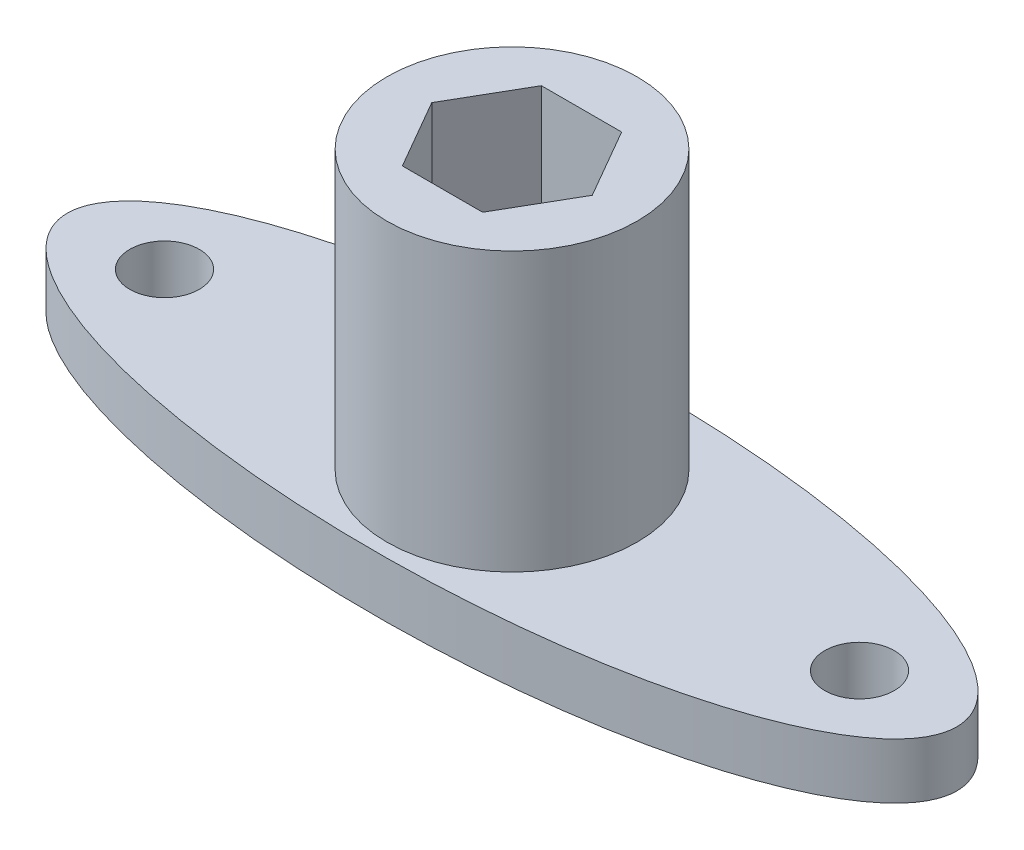
SolidWorks part; units mm, degrees
ref_plane "Front Plane" through (0, 0, 0) normal (0, 0, 1) x (1, 0, 0)
ref_plane "Top Plane" through (0, 0, 0) normal (0, 1, 0) x (1, 0, 0)
ref_plane "Right Plane" through (0, 0, 0) normal (1, 0, 0) x (0, 0, -1)
sketch "Sketch1" plane through (0, 0, 0) normal (0, 1, 0) x (1, 0, 0)
  line L0 (0, 0) -> (0, 8.2104) construction
  line L2 (3.6662, 0) -> (1.8331, 3.175)
  line L3 (1.8331, 3.175) -> (-1.8331, 3.175)
  line L4 (-1.8331, 3.175) -> (-3.6662, 0)
  line L5 (-3.6662, 0) -> (-1.8331, -3.175)
  line L6 (-1.8331, -3.175) -> (1.8331, -3.175)
  line L7 (1.8331, -3.175) -> (3.6662, 0)
  circle A0 centre (-15.875, 0) radius 1.5875
  circle A1 centre (15.875, 0) radius 1.5875
  circle A2 centre (0, 0) radius 5.715
  circle A3 centre (0, 0) radius 3.175 construction
  ellipse E0 centre (0, 0) end of major axis (20.32, 0) minor radius 6.35
  point P14 (0, 0)
  dimension "D3" = 4.445
  dimension "D4" = 3.175
  dimension "D5" = 11.43
  dimension "D1" = 12.7
  dimension "D2" = 40.64
  dimension "D6" = 6.35
extrude "Boss-Extrude1" add sketch "Sketch1" along normal blind 2.54 contours E0 A1 A0 A2 | A2 L7 L6 L5 L4 L3 L2 | L2 L3 L4 L5 L6 L7 region at (-5.5534, 0, 0) region at (-19.8839, 0, 0.179)
extrude "Boss-Extrude3" add sketch "Sketch1<4>" along normal blind 15.24 contours A2 L7 L6 L5 L4 L3 L2 region at (-5.5534, 0, 0)
sketch "Sketch1<4>" plane through (0, 0, 0) normal (0, 1, 0) x (1, 0, 0) same geometry as "Sketch1"
extrude "Boss-Extrude4" add sketch "Sketch1<5>" along normal blind 7.62 contours L6 L7 L2 L3 L4 L5 region at (0, 0, 0)
sketch "Sketch1<5>" plane through (0, 0, 0) normal (0, 1, 0) x (1, 0, 0) same geometry as "Sketch1"
